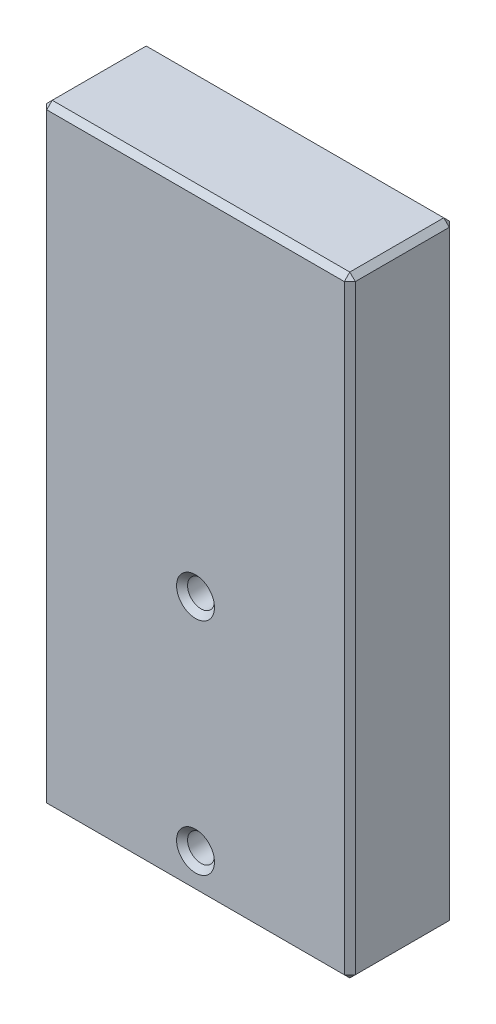
SolidWorks part; units mm, degrees
ref_plane "Front Plane" through (0, 0, 0) normal (0, 0, 1) x (1, 0, 0)
ref_plane "Top Plane" through (0, 0, 0) normal (0, 1, 0) x (1, 0, 0)
ref_plane "Right Plane" through (0, 0, 0) normal (1, 0, 0) x (0, 0, -1)
sketch "Sketch1" plane through (0, 0, 0) normal (0, 0, 1) x (1, 0, 0)
  line L1 (0, 0) -> (28, 0)
  line L2 (0, 0) -> (0, 55.475)
  line L3 (0, 55.475) -> (28, 55.475)
  line L4 (28, 0) -> (28, 55.475)
  dimension "D1" = 28
  dimension "D2" = 55.475
extrude "Boss-Extrude1" add sketch "Sketch1" along normal blind 9.525
sketch "Sketch2" plane through (0, 0, 0) normal (0, -1, 0) x (1, 0, 0)
  line L0 (0, 0) -> (28, 0) construction
  line L1 (0, 9.525) -> (0, 0) construction
  circle A0 centre (5, 4.7625) radius 1.2195
  circle A3 centre (23, 4.7625) radius 1.2195
  dimension "D1" = 2.439
  dimension "D6" = 2.439
  dimension "D2" = 4.7625
  dimension "D3" = 5
  dimension "D4" = 18
extrude "Cut-Extrude1" cut sketch "Sketch2" against normal blind 20
sketch "Sketch3" plane through (0, 0, 9.525) normal (0, 0, 1) x (1, 0, 0)
  line L0 (22.85, 65) -> (5.15, 65)
  line L1 (5.15, 65) -> (5.15, 0)
  line L2 (5.15, 0) -> (22.85, 0)
  line L3 (22.85, 0) -> (22.85, 65)
  line L4 (0, 55.475) -> (0, 0) construction
  circle A0 centre (14, 3.475) radius 1.7
  circle A1 centre (14, 3.475) radius 1.2195
  circle A2 centre (14, 23.475) radius 1.7
  circle A3 centre (14, 23.475) radius 1.2195
  dimension "D6" = 2.439
  dimension "D7" = 3.4
  dimension "D8" = 3.4
  dimension "D9" = 2.439
  dimension "D1" = 3.475
  dimension "D2" = 23.475
  dimension "D3" = 8.85
  dimension "D4" = 65
  dimension "D5" = 17.7
  dimension "D10" = 0
  dimension "D11" = 14
extrude "Cut-Extrude2" cut sketch "Sketch3" against normal through all contours A3 | A1 region at (14, 3.475, 9.525) region at (14, 23.475, 9.525)
chamfer "Chamfer1" distance 0.5 angle 45 12 edges at (14, 0, 0) (28, 0, 4.7625) (28, 27.7375, 0) (14, 55.475, 0) (28, 55.475, 4.7625) (28, 27.7375, 9.525) (14, 55.475, 9.525) (14, 0, 9.525) (0, 0, 4.7625) (0, 27.7375, 0) (0, 55.475, 4.7625) (0, 27.7375, 9.525)
chamfer "Chamfer2" distance 0.5 angle 45 6 edges at (23, 0, 3.543) (5, 0, 3.543) (15.2195, 3.475, 0) (15.2195, 23.475, 0) (15.2195, 3.475, 9.525) (15.2195, 23.475, 9.525)
